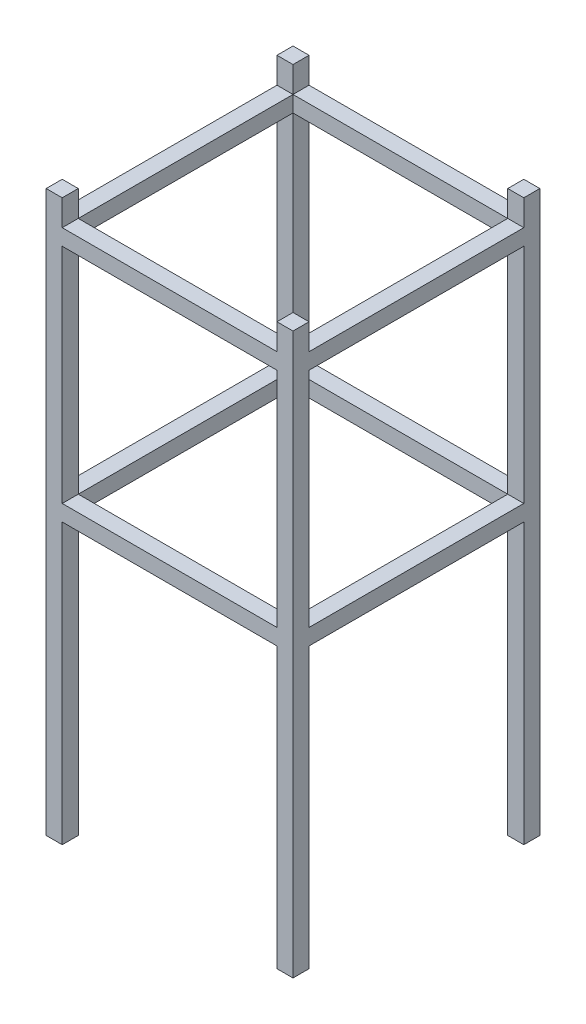
SolidWorks part; units mm, degrees
ref_plane "Front Plane" through (0, 0, 0) normal (0, 0, 1) x (1, 0, 0)
ref_plane "Top Plane" through (0, 0, 0) normal (0, 1, 0) x (1, 0, 0)
ref_plane "Right Plane" through (0, 0, 0) normal (1, 0, 0) x (0, 0, -1)
sketch "Sketch2" plane through (0, 0, 0) normal (0, 1, 0) x (1, 0, 0)
  line L0 (-50, 0) -> (50, 0) construction
  line L1 (0, -55) -> (0, 55) construction
  line L2 (0, -50) -> (0, 50) construction
  line L3 (-55, 0) -> (55, 0) construction
  line L5 (-50, 50) -> (50, 50) construction
  line L6 (-50, 50) -> (-50, -50) construction
  line L7 (-50, -50) -> (50, -50) construction
  line L8 (50, 50) -> (50, -50) construction
  point P6 (0, 0)
  point P11 (0, 0)
sketch "Sketch3" plane through (0, 0, 0) normal (0, 1, 0) x (1, 0, 0)
  line L0 (0, -55) -> (0, 55) construction
  line L1 (-50, 50) -> (-43.5, 50)
  line L2 (-50, 50) -> (-50, 43.5)
  line L3 (-50, 43.5) -> (-43.5, 43.5)
  line L4 (-43.5, 50) -> (-43.5, 43.5)
  line L5 (50, 43.5) -> (43.5, 43.5)
  line L6 (43.5, 50) -> (43.5, 43.5)
  line L7 (50, 50) -> (43.5, 50)
  line L8 (50, 50) -> (50, 43.5)
  line L9 (-55, 0) -> (55, 0) construction
  line L10 (50, -50) -> (50, -43.5)
  line L11 (50, -50) -> (43.5, -50)
  line L12 (43.5, -50) -> (43.5, -43.5)
  line L13 (50, -43.5) -> (43.5, -43.5)
  line L14 (-50, -43.5) -> (-43.5, -43.5)
  line L15 (-43.5, -50) -> (-43.5, -43.5)
  line L16 (-50, -50) -> (-43.5, -50)
  line L17 (-50, -50) -> (-50, -43.5)
extrude "Boss-Extrude1" add sketch "Sketch3" along normal blind 200
sketch "Sketch11" plane through (0, 200, 0) normal (0, 1, 0) x (1, 0, 0)
  line L1 (-43.5, 43.5) -> (43.5, 43.5)
  line L2 (-43.5, 43.5) -> (-43.5, -43.5)
  line L3 (-43.5, -43.5) -> (43.5, -43.5)
  line L4 (43.5, 43.5) -> (43.5, -43.5)
  line L5 (-50, 50) -> (50, 50)
  line L6 (-50, 50) -> (-50, -50)
  line L7 (-50, -50) -> (50, -50)
  line L8 (50, 50) -> (50, -50)
extrude "Boss-Extrude7" add sketch "Sketch11" against normal blind 6.5
sketch "Sketch12" plane through (0, 200, 0) normal (0, 1, 0) x (1, 0, 0)
  line L1 (-43.5, 43.5) -> (43.5, 43.5)
  line L2 (-43.5, 43.5) -> (-43.5, -43.5)
  line L3 (-43.5, -43.5) -> (43.5, -43.5)
  line L4 (43.5, 43.5) -> (43.5, -43.5)
  line L5 (-50, 50) -> (50, 50)
  line L6 (-50, 50) -> (-50, -50)
  line L7 (-50, -50) -> (50, -50)
  line L8 (50, 50) -> (50, -50)
extrude "Boss-Extrude8" add sketch "Sketch12" along normal blind 3.25 and the other way blind 3.25 from offset 100 offset against normal yes
sketch "Sketch13" plane through (0, 200, 0) normal (0, 1, 0) x (1, 0, 0)
  line L0 (0, -55) -> (0, 55) construction
  line L1 (-50, 50) -> (-43.5, 50)
  line L2 (-50, 50) -> (-50, 43.5)
  line L3 (-50, 43.5) -> (-43.5, 43.5)
  line L4 (-43.5, 50) -> (-43.5, 43.5)
  line L5 (50, 43.5) -> (43.5, 43.5)
  line L6 (43.5, 50) -> (43.5, 43.5)
  line L7 (50, 50) -> (43.5, 50)
  line L8 (50, 50) -> (50, 43.5)
  line L9 (-55, 0) -> (55, 0) construction
  line L10 (50, -50) -> (50, -43.5)
  line L11 (50, -50) -> (43.5, -50)
  line L12 (43.5, -50) -> (43.5, -43.5)
  line L13 (50, -43.5) -> (43.5, -43.5)
  line L14 (-50, -43.5) -> (-43.5, -43.5)
  line L15 (-43.5, -50) -> (-43.5, -43.5)
  line L16 (-50, -50) -> (-43.5, -50)
  line L17 (-50, -50) -> (-50, -43.5)
extrude "Boss-Extrude9" add sketch "Sketch13" along normal blind 10.5
sketch "Sketch14" plane through (0, 0, 0) normal (0, -1, 0) x (1, 0, 0)
  line L0 (0, -55) -> (0, 55) construction
  line L1 (-50, 50) -> (-43.5, 50)
  line L2 (-50, 50) -> (-50, 43.5)
  line L3 (-50, 43.5) -> (-43.5, 43.5)
  line L4 (-43.5, 50) -> (-43.5, 43.5)
  line L5 (50, 43.5) -> (43.5, 43.5)
  line L6 (43.5, 50) -> (43.5, 43.5)
  line L7 (50, 50) -> (43.5, 50)
  line L8 (50, 50) -> (50, 43.5)
  line L9 (55, 0) -> (-55, 0) construction
  line L10 (50, -50) -> (50, -43.5)
  line L11 (50, -50) -> (43.5, -50)
  line L12 (43.5, -50) -> (43.5, -43.5)
  line L13 (50, -43.5) -> (43.5, -43.5)
  line L14 (-50, -43.5) -> (-43.5, -43.5)
  line L15 (-43.5, -50) -> (-43.5, -43.5)
  line L16 (-50, -50) -> (-43.5, -50)
  line L17 (-50, -50) -> (-50, -43.5)
extrude "Boss-Extrude10" add sketch "Sketch14" along normal blind 16.5
